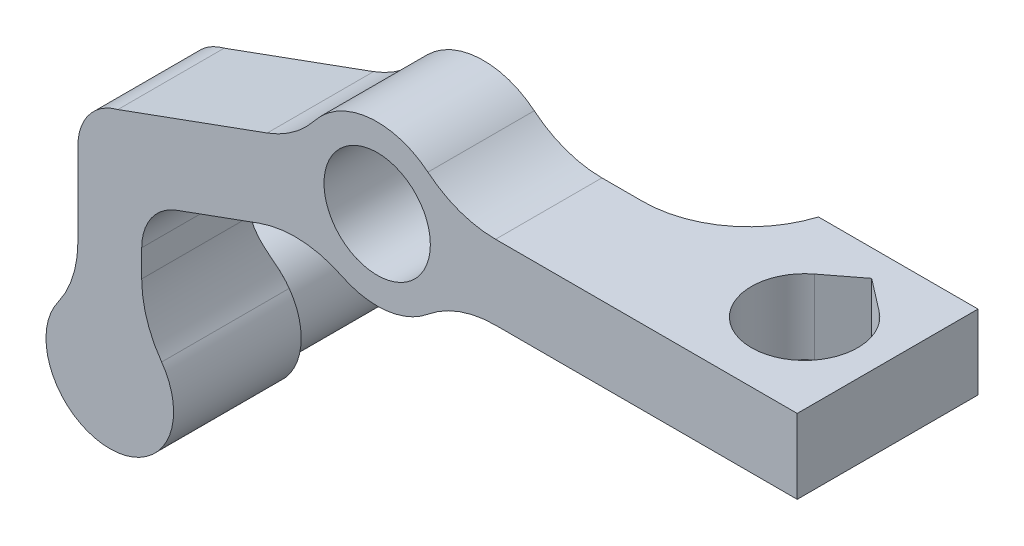
SolidWorks part; units mm, degrees
ref_plane "Alzado" through (0, 0, 0) normal (0, 0, 1) x (1, 0, 0)
ref_plane "Planta" through (0, 0, 0) normal (0, 1, 0) x (1, 0, 0)
ref_plane "Vista lateral" through (0, 0, 0) normal (1, 0, 0) x (0, 0, -1)
sketch "Croquis1" plane through (0, 0, 0) normal (0, 0, 1) x (1, 0, 0)
  circle A0 centre (0, 0) radius 5
  circle A1 centre (0, 0) radius 7.5
  dimension "D1" = 10
  dimension "D2" = 15
extrude "Saliente-Extruir1" add sketch "Croquis1" along normal mid plane 10
sketch3d "Croquis3D1"
  line L0 (0, 0, 0) -> (-4, 0, 0) construction
  line L1 (0, 0, 0) -> (4, 0, 0) construction
  line L2 (-4, 0, 0) -> (-25.1431, -7.6955, 0) construction
  line L3 (-4, 0, 0) -> (-25.1431, 0, 0) construction
  line L4 (-25.1431, 0, 0) -> (-25.1431, -7.6955, 0) construction
  line L5 (4, 0, 0) -> (31.8935, 0, 2.4404) construction
  line L6 (31.8935, 0, 2.4404) -> (4, 0, 2.4404) construction
  line L7 (4, 0, 2.4404) -> (4, 0, 0) construction
  line L8 (4, 0, 2.4404) -> (32, 0, 2.4404) construction
  line L9 (32, 0, 2.4404) -> (32, 0, 0) construction
  line L10 (32, 0, 0) -> (4, 0, 0) construction
  dimension "D1" = 4
  dimension "D2" = 4
  dimension "D3" = 22.5
  dimension "D4" = 20
  dimension "D5" = 85
  dimension "D6" = 28
  dimension "D7" = 28
ref_plane "Plano1" through (-25.1431, -7.6955, 0) normal (-0.9397, -0.342, 0) x (0, 0, 1)
sketch "Croquis23" plane through (-25.1431, -7.6955, 0) normal (-0.9397, -0.342, 0) x (0, 0, 1)
  line L1 (-5, 3.5) -> (5, 3.5)
  line L2 (-5, 3.5) -> (-5, -3.5)
  line L3 (-5, -3.5) -> (5, -3.5)
  line L4 (5, 3.5) -> (5, -3.5)
  line L5 (-5, 3.5) -> (5, -3.5) construction
  line L6 (-5, -3.5) -> (5, 3.5) construction
  point P0 (0, 0)
  dimension "D1" = 7
  dimension "D2" = 10
extrude "Saliente-Extruir15" add sketch "Croquis23" against normal blind 21
ref_plane "Plano2" through (32, 0, 0) normal (1, 0, 0) x (0, 0, -1)
sketch "Croquis3" plane through (32, 0, 0) normal (1, 0, 0) x (0, 0, -1)
  line L1 (-5, 3.5) -> (5, 3.5)
  line L2 (-5, 3.5) -> (-5, -3.5)
  line L3 (-5, -3.5) -> (5, -3.5)
  line L4 (5, 3.5) -> (5, -3.5)
  line L5 (-5, 3.5) -> (5, -3.5) construction
  line L6 (-5, -3.5) -> (5, 3.5) construction
  point P0 (0, 0)
  dimension "D1" = 10
  dimension "D2" = 7
extrude "Saliente-Extruir3" add sketch "Croquis3" against normal up to surface (25.3668 mm away) up to face at (0.4498, 0.0634, 0)
ref_plane "Plano3" through (-25.1431, -7.6955, 0) normal (0, 1, 0) x (1, 0, 0)
sketch "Croquis7" plane through (-25.1431, -7.6955, 0) normal (0, 1, 0) x (1, 0, 0)
  line L1 (-3, -5) -> (3, -5)
  line L2 (-3, -5) -> (-3, 5)
  line L3 (-3, 5) -> (3, 5)
  line L4 (3, -5) -> (3, 5)
  line L5 (-3, -5) -> (3, 5) construction
  line L6 (-3, 5) -> (3, -5) construction
  point P0 (0, 0)
  dimension "D1" = 6
  dimension "D2" = 10
extrude "Saliente-Extruir7" add sketch "Croquis7" along normal mid plane 8
sketch "Croquis20" plane through (0, 0, 5) normal (0, 0, -1) x (-1, 0, 0)
  line L1 (-39.5, 3.5) -> (-24.5, 3.5)
  line L2 (-39.5, 3.5) -> (-39.5, -3.5)
  line L3 (-39.5, -3.5) -> (-24.5, -3.5)
  line L4 (-24.5, 3.5) -> (-24.5, -3.5)
  line L5 (-39.5, 3.5) -> (-24.5, -3.5) construction
  line L6 (-39.5, -3.5) -> (-24.5, 3.5) construction
  point P0 (-32, 0)
  dimension "D1" = 7
  dimension "D2" = 15
extrude "Saliente-Extruir13" add sketch "Croquis20" along normal blind 17
sketch "Croquis21" plane through (0, -3.5, 0) normal (0, -1, 0) x (1, 0, 0)
  line L2 (32, -9.5) -> (28.9523, -7.1566)
  line L3 (32, -12) -> (32, -9.5) construction
  line L4 (39.5, -12) -> (24.5, -12) construction
  line L5 (32, -9.5) -> (32, -3.1929) construction
  line L6 (32, -9.5) -> (35.0477, -7.1566)
  arc A1 (35.0477, -7.1566) -> (28.9523, -7.1566) centre (32, -3.1929) ccw
  dimension "D1" = 2.5
  dimension "D3" = 10
extrude "Cortar-Extruir3" cut sketch "Croquis21" against normal through all
ref_plane "Plano4" through (-25.1431, 0, 0) normal (1, 0, 0) x (0, 0, -1)
sketch "Croquis8" plane through (-25.1431, 0, 0) normal (1, 0, 0) x (0, 0, -1)
  line L0 (5, -11.6955) -> (5, -17.6955)
  line L4 (-5, -17.6955) -> (-5, -11.6955)
  line L5 (-5, -11.6955) -> (5, -11.6955)
  line L7 (-5, -26.6955) -> (-5, -17.6955)
  line L8 (5, -17.6955) -> (5, -26.6955)
  line L11 (5, -26.6955) -> (-5, -26.6955)
  dimension "D1" = 15
  dimension "D2" = 6
extrude "Saliente-Extruir8" add sketch "Croquis8" along normal mid plane 6
sketch "Croquis9" plane through (0, 0, 5) normal (0, 0, 1) x (1, 0, 0)
  line L0 (-25.1431, -17.6955) -> (-25.1431, -25.6955) construction
  line L2 (-25.1431, -25.6955) -> (-25.1431, -28.6955) construction
  circle A0 centre (-25.1431, -25.6955) radius 6
  dimension "D2" = 12
  dimension "D1" = 3
extrude "Saliente-Extruir9" add sketch "Croquis9" against normal blind 12
sketch "Croquis24" plane through (0, 0, -7) normal (0, 0, 1) x (1, 0, 0)
  circle A0 centre (-25.1431, -25.6955) radius 5
  dimension "D1" = 10
extrude "Saliente-Extruir16" add sketch "Croquis24" against normal blind 23
fillet "Redondeo3" radius 5 1 edges at (-22.1431, -10.3282, 0)
fillet "Redondeo4" radius 5 1 edges at (-28.1431, -3.6955, 0)
fillet "Redondeo5" radius 10 8 edges at (-22.1431, -20.4993, 0) (-28.1431, -20.4993, 0) (-6.0278, -4.4627, 0) (6.6332, -3.5, 0) (6.6332, 3.5, 0) (-7.0263, 2.6231, 0) (24.5, 0, -5) (-25.1431, -19.6955, -5)
